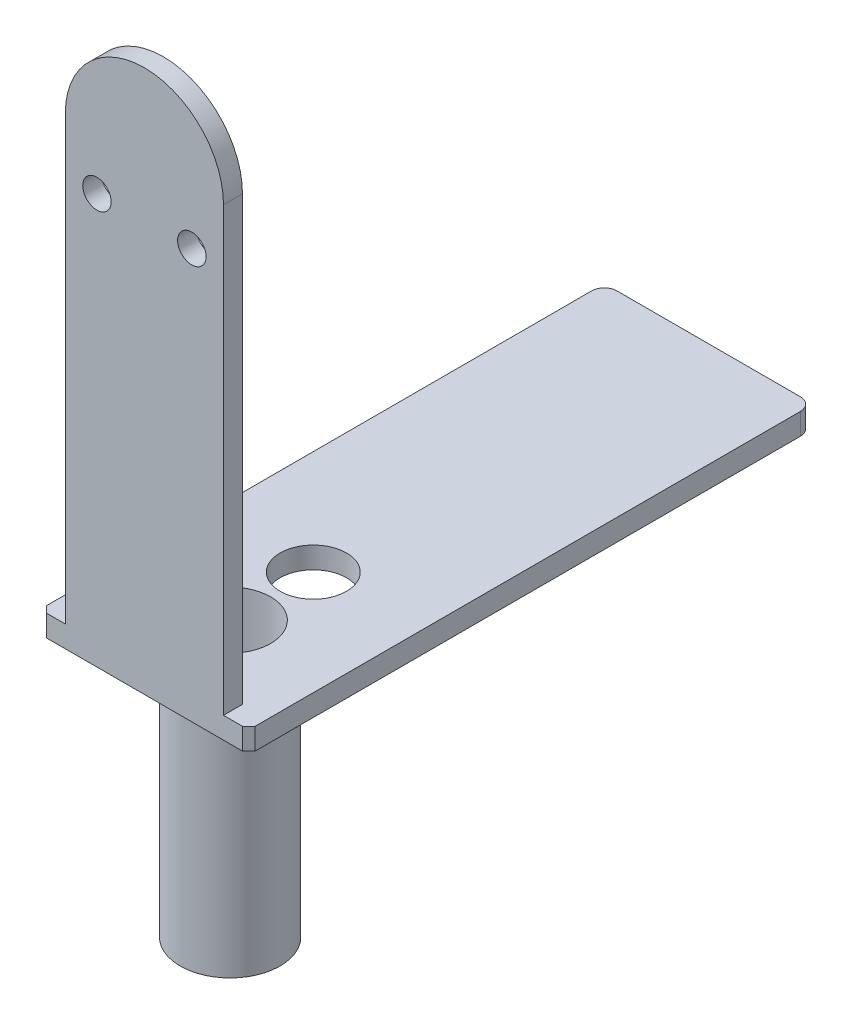
SolidWorks part; units mm, degrees
ref_plane "Front Plane" through (0, 0, 0) normal (0, 0, 1) x (1, 0, 0)
ref_plane "Top Plane" through (0, 0, 0) normal (0, 1, 0) x (1, 0, 0)
ref_plane "Right Plane" through (0, 0, 0) normal (1, 0, 0) x (0, 0, -1)
sketch "Sketch1" plane through (0, 0, 0) normal (0, 0, 1) x (1, 0, 0)
  line L0 (0, 0) -> (33, 0)
  line L1 (16.5, 0) -> (29, 0)
  line L2 (16.5, 0) -> (16.5, 9.4766)
  line L3 (4, 0) -> (4, 80.5)
  line L4 (29, 0) -> (29, 80.5)
  line L5 (0, 0) -> (0, 80.5)
  line L6 (0, 80.5) -> (4, 80.5)
  line L7 (33, 0) -> (33, 80.5)
  line L8 (33, 80.5) -> (29, 80.5)
  arc A0 (33, 80.5) -> (0, 80.5) centre (16.5, 80.5) ccw
  arc A1 (4, 80.5) -> (29, 80.5) centre (16.5, 80.5) cw
  point P5 (4, 0)
  dimension "D1" = 33
  dimension "D2" = 12.5
  dimension "D3" = 80.5
extrude "Boss-Extrude1" add sketch "Sketch1" along normal blind 71 contours L6 L5 L0 L3 | L6 A1 L8 A0 | L7 L8 L4 L0 region at (2, 40.25, 0) region at (16.5, 96.631, 0) region at (31, 40.25, 0)
sketch "Sketch2" plane through (0, 0, 71) normal (0, 0, 1) x (1, 0, 0)
  line L2 (33, 48.5) -> (0, 48.5)
  line L3 (0, 0) -> (0, 80.5) construction
  line L4 (0, 48.5) -> (0, 80.5)
  line L5 (33, 0) -> (33, 80.5) construction
  line L6 (33, 48.5) -> (33, 80.5)
  arc A0 (33, 80.5) -> (0, 80.5) centre (16.5, 80.5) ccw construction
  arc A1 (33, 80.5) -> (0, 80.5) centre (16.5, 80.5) ccw
  point P8 (16.5, 48.5)
extrude "Boss-Extrude2" add sketch "Sketch2" against normal blind 4
sketch "Sketch3" plane through (0, 0, 67) normal (0, 0, -1) x (-1, 0, 0)
  line L0 (-4, 48.5) -> (-29, 48.5) construction
  line L1 (-4, 48.5) -> (-29, 48.5)
  line L3 (-29, 44.5) -> (-4, 44.5)
  line L5 (0, 0) -> (0, 80.5) construction
  line L6 (0, 0) -> (0, 48.5)
  line L7 (-4, 48.5) -> (0, 48.5)
  line L8 (0, 0) -> (-3.8379, 0)
  line L9 (-4, 44.5) -> (-3.8379, 0)
  line L10 (-16.5, 44.5) -> (-16.5, 41.0104)
  line L11 (-33, 0) -> (-33, 48.5)
  line L12 (-29, 48.5) -> (-33, 48.5)
  line L13 (-29, 44.5) -> (-29.1621, 0)
  line L14 (-33, 0) -> (-29.1621, 0)
  line M8 (-29, 48.5) -> (-4, 48.5)
extrude "Boss-Extrude3" add sketch "Sketch3" against normal blind 34.2 contours L11 L14 L13 L3 L9 L8 L6 L7 L12 M8 region at (2, 47.9134, 67)
sketch "Sketch4" plane through (0, 0, 0) normal (0, 0, -1) x (-1, 0, 0)
  line L6 (-4, 80.5) -> (-4, 0)
  line L7 (-4, 0) -> (0, 0)
  line L8 (0, 0) -> (0, 80.5)
  line L9 (-33, 80.5) -> (-33, 0)
  line L10 (-33, 0) -> (-29, 0)
  line L11 (-29, 0) -> (-29, 80.5)
  line L12 (-4, 80.5) -> (-4, 0)
  line L13 (-4, 0) -> (0, 0)
  line L14 (0, 0) -> (0, 80.5)
  line L15 (-33, 80.5) -> (-33, 0)
  line L16 (-33, 0) -> (-29, 0)
  line L17 (-29, 0) -> (-29, 80.5)
  arc A2 (0, 80.5) -> (-33, 80.5) centre (-16.5, 80.5) ccw
  arc A3 (-4, 80.5) -> (-29, 80.5) centre (-16.5, 80.5) ccw
  arc A4 (0, 80.5) -> (-33, 80.5) centre (-16.5, 80.5) ccw
  arc A5 (-4, 80.5) -> (-29, 80.5) centre (-16.5, 80.5) ccw
  dimension "D1" = 0
extrude "Cut-Extrude1" cut sketch "Sketch4" against normal blind 13
sketch "Sketch5" plane through (0, 0, 71) normal (0, 0, 1) x (1, 0, 0)
  line L0 (0, 80.5) -> (33, 80.5)
  circle A0 centre (16.5, 80.5) radius 10
  dimension "D1" = 20
extrude "Cut-Extrude2" cut sketch "Sketch5" against normal blind 13 contours L0 A0 | L0 A0 region at (16.5, 84.7441, 71) region at (16.5, 76.2559, 71)
sketch "Sketch6" plane through (0, 0, 71) normal (0, 0, 1) x (1, 0, 0)
  line L0 (16.5, 70.5) -> (16.5, 73.1374)
  line L1 (16.5, 70.5) -> (33, 70.5)
  line L2 (33, 48.5) -> (33, 80.5) construction
  circle A0 centre (26.5, 70.5) radius 1.7
  circle A1 centre (6.5, 70.5) radius 1.7
  dimension "D2" = 3.4
  dimension "D1" = 6.5
extrude "Cut-Extrude3" cut sketch "Sketch6" against normal blind 13 contours A1 | L1 A0 | L1 A0 region at (26.5, 71.2215, 71) region at (26.5, 69.7785, 71) region at (6.5, 70.5, 71)
sketch "Sketch7" plane through (0, 0, 71) normal (0, 0, 1) x (1, 0, 0)
  circle A0 centre (6.5, 70.5) radius 3.25
  circle A1 centre (26.5, 70.5) radius 3.25
  dimension "D1" = 6.5
extrude "Cut-Extrude4" cut sketch "Sketch7" against normal blind 2.5
sketch "Sketch9" plane through (0, 0, 0) normal (0, -1, 0) x (1, 0, 0)
  line L0 (29.1621, 101.2) -> (29.1621, 71) construction
  line L1 (29.1621, 101.2) -> (29.1621, 71)
  line L2 (29.1621, 71) -> (29, 71)
  line L3 (29, 71) -> (29, 120)
  line L4 (29, 120) -> (29.1621, 101.2)
  line L6 (29, 67) -> (4, 67) construction
  line L7 (29, 67) -> (4, 67)
  line L8 (16.5, 67) -> (16.5, 71)
  line L9 (4, 120) -> (3.8379, 101.2)
  line L10 (4, 71) -> (4, 120)
  line L11 (3.8379, 71) -> (4, 71)
  line L12 (3.8379, 101.2) -> (3.8379, 71)
extrude "Boss-Extrude4" add sketch "Sketch9" against normal up to surface (44.5 mm away) contours L4 L1 L2 L3 | L9 L12 L11 L10 up to face at (16.5, 44.5, 79.7333)
sketch "Sketch10" plane through (0, 0, 101.2) normal (0, 0, 1) x (1, 0, 0)
  line L1 (40.2439, -6.5645) -> (-5.7585, -6.5645)
  line L2 (40.2439, -6.5645) -> (40.2439, 55.1467)
  line L3 (40.2439, 55.1467) -> (-5.7585, 55.1467)
  line L4 (-5.7585, -6.5645) -> (-5.7585, 55.1467)
  line L5 (40.2439, -6.5645) -> (-5.7585, 55.1467) construction
  line L6 (40.2439, 55.1467) -> (-5.7585, -6.5645) construction
  point P0 (17.2427, 24.2911)
extrude "Cut-Extrude5" cut sketch "Sketch10" along normal blind 42
fillet "Fillet1" radius 18 2 edges at (16.5, 44.5, 67) (16.5, 48.5, 71)
sketch "Sketch11" plane through (0, 0, 101.2) normal (0, 0, 1) x (1, 0, 0)
  line L0 (29, 0) -> (4, 0)
  line L8 (4, 44.5) -> (29, 44.5)
  line L9 (29, 44.5) -> (29, 0)
  line L10 (29, 0) -> (33, 0)
  line L11 (33, 0) -> (33, 48.5)
  line L12 (33, 48.5) -> (0, 48.5)
  line L13 (0, 48.5) -> (0, 0)
  line L14 (0, 0) -> (4, 0)
  line L15 (4, 0) -> (4, 44.5)
  line L18 (29, 0) -> (33, 0)
  line L19 (33, 0) -> (33, 48.5)
  line L20 (33, 48.5) -> (0, 48.5)
  line L21 (0, 48.5) -> (0, 0)
  line L22 (0, 0) -> (4, 0)
  dimension "D1" = 0
extrude "Boss-Extrude5" add sketch "Sketch11" along normal blind 4
fillet "Fillet3" radius 16.2 1 edges at (16.5, 48.5, 105.2)
fillet "Fillet4" radius 14 1 edges at (16.5, 44.5, 101.2)
sketch "Sketch12" plane through (0, 0, 0) normal (0, -1, 0) x (1, 0, 0)
  line L8 (4, 13) -> (4, 101.2)
  line L9 (4, 101.2) -> (29, 101.2)
  line L10 (29, 101.2) -> (29, 13)
  line L11 (29, 13) -> (33, 13)
  line L12 (33, 13) -> (33, 105.2)
  line L13 (33, 105.2) -> (0, 105.2)
  line L14 (0, 105.2) -> (0, 13)
  line L15 (0, 13) -> (4, 13)
  line L16 (4, 13) -> (4, 101.2)
  line L17 (4, 101.2) -> (29, 101.2)
  line L18 (29, 101.2) -> (29, 13)
  line L19 (29, 13) -> (33, 13)
  line L20 (33, 13) -> (33, 105.2)
  line L21 (33, 105.2) -> (0, 105.2)
  line L22 (0, 105.2) -> (0, 13)
  line L23 (0, 13) -> (4, 13)
  dimension "D1" = 0
extrude "Cut-Extrude6" cut sketch "Sketch12" against normal blind 10.6
sketch "Sketch13" plane through (0, 0, 13) normal (0, 0, -1) x (-1, 0, 0)
  line L6 (-33, 80.5) -> (-33, 10.6)
  line L7 (-33, 10.6) -> (-29, 10.6)
  line L8 (-29, 10.6) -> (-29, 80.5)
  line L9 (-4, 80.5) -> (-4, 10.6)
  line L10 (-4, 10.6) -> (0, 10.6)
  line L11 (0, 10.6) -> (0, 80.5)
  line L12 (-33, 80.5) -> (-33, 10.6)
  line L13 (-33, 10.6) -> (-29, 10.6)
  line L14 (-29, 10.6) -> (-29, 80.5)
  line L15 (-4, 80.5) -> (-4, 10.6)
  line L16 (-4, 10.6) -> (0, 10.6)
  line L17 (0, 10.6) -> (0, 80.5)
  arc A2 (-4, 80.5) -> (-29, 80.5) centre (-16.5, 80.5) ccw
  arc A3 (0, 80.5) -> (-33, 80.5) centre (-16.5, 80.5) ccw
  arc A4 (-4, 80.5) -> (-29, 80.5) centre (-16.5, 80.5) ccw
  arc A5 (0, 80.5) -> (-33, 80.5) centre (-16.5, 80.5) ccw
  dimension "D1" = 0
extrude "Boss-Extrude6" add sketch "Sketch13" along normal blind 4
ref_plane "Plane1" through (0, 0, 13) normal (0, 0, -1) x (-1, 0, 0)
sketch "Sketch14" plane through (0, 0, 13) normal (0, 0, -1) x (-1, 0, 0)
  line L0 (-29, 10.6) -> (-4, 10.6)
  line L6 (-33, 80.5) -> (-33, 10.6)
  line L7 (-33, 10.6) -> (-29, 10.6)
  line L8 (-29, 10.6) -> (-29, 80.5)
  line L9 (-4, 80.5) -> (-4, 10.6)
  line L10 (-4, 10.6) -> (0, 10.6)
  line L11 (0, 10.6) -> (0, 80.5)
  line L12 (-33, 80.5) -> (-33, 10.6)
  line L13 (-33, 10.6) -> (-29, 10.6)
  line L16 (-4, 10.6) -> (0, 10.6)
  line L17 (0, 10.6) -> (0, 80.5)
  arc A2 (0, 80.5) -> (-33, 80.5) centre (-16.5, 80.5) ccw
  arc A3 (-4, 80.5) -> (-29, 80.5) centre (-16.5, 80.5) ccw
  arc A4 (0, 80.5) -> (-33, 80.5) centre (-16.5, 80.5) ccw
  dimension "D1" = 0
extrude "Cut-Extrude7" cut sketch "Sketch14" against normal blind 148
sketch "Sketch15" plane through (0, 0, 13) normal (0, 0, 1) x (1, 0, 0)
  line L0 (4, 10.6) -> (29, 10.6)
  line L6 (29, 80.5) -> (29, 10.6)
  line L7 (29, 10.6) -> (33, 10.6)
  line L8 (33, 10.6) -> (33, 80.5)
  line L9 (0, 80.5) -> (0, 10.6)
  line L10 (0, 10.6) -> (4, 10.6)
  line L11 (4, 10.6) -> (4, 80.5)
  line L12 (29, 80.5) -> (29, 10.6)
  line L13 (29, 10.6) -> (33, 10.6)
  line L17 (4, 10.6) -> (4, 80.5)
  arc A2 (33, 80.5) -> (0, 80.5) centre (16.5, 80.5) ccw
  arc A3 (29, 80.5) -> (4, 80.5) centre (16.5, 80.5) ccw
  arc A5 (29, 80.5) -> (4, 80.5) centre (16.5, 80.5) ccw
  line M10 (29, 80.5) -> (29, 10.6)
  line M16 (4, 10.6) -> (4, 80.5)
  arc M17 (4, 80.5) -> (29, 80.5) centre (16.5, 80.5) cw
  dimension "D1" = 0
extrude "Boss-Extrude7" add sketch "Sketch15" along normal blind 3 separate body contours L0 M16 M10 M17 region at (16.5, 50.5076, 13)
sketch "Sketch16" plane through (0, 0, 9) normal (0, 0, -1) x (-1, 0, 0)
  line L6 (-33, 80.5) -> (-33, 10.6)
  line L7 (-33, 10.6) -> (-29, 10.6)
  line L8 (-29, 10.6) -> (-29, 80.5)
  line L9 (-4, 80.5) -> (-4, 10.6)
  line L10 (-4, 10.6) -> (0, 10.6)
  line L11 (0, 10.6) -> (0, 80.5)
  line L12 (-33, 80.5) -> (-33, 10.6)
  line L13 (-33, 10.6) -> (-29, 10.6)
  line L14 (-29, 10.6) -> (-29, 80.5)
  line L15 (-4, 80.5) -> (-4, 10.6)
  line L16 (-4, 10.6) -> (0, 10.6)
  line L17 (0, 10.6) -> (0, 80.5)
  arc A2 (0, 80.5) -> (-33, 80.5) centre (-16.5, 80.5) ccw
  arc A3 (-4, 80.5) -> (-29, 80.5) centre (-16.5, 80.5) ccw
  arc A4 (0, 80.5) -> (-33, 80.5) centre (-16.5, 80.5) ccw
  arc A5 (-4, 80.5) -> (-29, 80.5) centre (-16.5, 80.5) ccw
  dimension "D1" = 0
extrude "Cut-Extrude8" cut sketch "Sketch16" against normal blind 14
sketch "Sketch17" plane through (0, 0, 13) normal (0, 0, -1) x (-1, 0, 0)
  line L0 (-16.5, 93) -> (-16.5, 68)
  line L1 (-16.5, 68) -> (-4, 68)
  line L2 (-4, 10.6) -> (-4, 80.5) construction
  arc A0 (-4, 80.5) -> (-29, 80.5) centre (-16.5, 80.5) ccw construction
  circle A1 centre (-9, 72) radius 2.25
  circle A2 centre (-24, 72) radius 2.25
  dimension "D2" = 4.5
  dimension "D3" = 5
  dimension "D4" = 4
  dimension "D1" = 25
extrude "Cut-Extrude9" cut sketch "Sketch17" against normal blind 14 contours A2 | A1 region at (24, 72, 13)
sketch "Sketch18" plane through (0, 10.6, 0) normal (0, -1, 0) x (1, 0, 0)
  line L0 (29, 16) -> (29, -76.2)
  line L1 (29, 16) -> (4, 16)
  line L2 (4, 16) -> (4, -76.2)
  line L3 (4, -76.2) -> (29, -76.2)
  dimension "D1" = 92.2
extrude "Boss-Extrude8" add sketch "Sketch18" along normal blind 4
sketch "Sketch19" plane through (0, 6.6, 0) normal (0, -1, 0) x (1, 0, 0)
  line L0 (4, 16) -> (0, 16)
  line L1 (0, 16) -> (0, -76.2)
  line L2 (4, -76.2) -> (0, -76.2)
  line L3 (4, -76.2) -> (4, 16)
  line L4 (16.5, 16) -> (16.5, 9.1971)
  line L5 (29, 16) -> (4, 16) construction
  line L6 (29, -76.2) -> (33, -76.2)
  line L7 (33, 16) -> (33, -76.2)
  line L8 (29, 16) -> (33, 16)
  line L9 (29, -76.2) -> (29, 16)
  line M7 (4, 16) -> (4, -76.2)
  line M9 (29, -76.2) -> (29, 16)
extrude "Boss-Extrude9" add sketch "Sketch19" against normal up to surface (4 mm away) contours L2 L0 L1 M7 | L8 L6 L7 M9 region at (2, 6.6, -30.1) region at (31, 6.6, -30.1) up to face at (16.5, 10.6, -31.6)
sketch "Sketch20" plane through (0, 6.6, 0) normal (0, -1, 0) x (1, 0, 0)
  line L0 (16.5, 16) -> (16.5, -10.7)
  line L1 (33, 16) -> (0, 16) construction
  circle A0 centre (16.5, -10.7) radius 5.25
  dimension "D2" = 10.5
  dimension "D1" = 26.7
extrude "Cut-Extrude10" cut sketch "Sketch20" against normal up to surface (4 mm away) contours A0 region at (12.8927, 6.6, -14.3073) up to face at (16.5, 10.6, -7.8)
sketch "Sketch21" plane through (0, 6.6, 0) normal (0, -1, 0) x (1, 0, 0)
  line L4 (33, 16) -> (0, 16)
  line L5 (0, 16) -> (0, -76.2)
  line L6 (0, -76.2) -> (33, -76.2)
  line L7 (33, -76.2) -> (33, 16)
  line L8 (33, 16) -> (0, 16)
  line L9 (0, 16) -> (0, -76.2)
  line L10 (0, -76.2) -> (33, -76.2)
  line L11 (33, -76.2) -> (33, 16)
  dimension "D1" = 0
extrude "Cut-Extrude11" cut sketch "Sketch21" against normal blind 0.6
sketch "Sketch22" plane through (0, 7.2, 0) normal (0, -1, 0) x (1, 0, 0)
  line L0 (16.5, 16) -> (16.5, 1.3)
  line L1 (33, 16) -> (0, 16) construction
  circle A0 centre (16.5, 1.3) radius 5.25
  dimension "D2" = 10.5
  dimension "D1" = 14.7
extrude "Cut-Extrude12" cut sketch "Sketch22" against normal up to surface (3.4 mm away) contours A0 region at (12.8927, 7.2, -2.3073) up to face at (16.5, 10.6, -15.95)
sketch "Sketch23" plane through (0, 7.2, 0) normal (0, -1, 0) x (1, 0, 0)
  line L0 (16.5, -5.45) -> (16.5, 10.35)
  circle A0 centre (16.5, -10.7) radius 5.25 construction
  circle A1 centre (16.5, 2.45) radius 7.9
  circle A2 centre (16.5, 2.45) radius 6.4
  dimension "D1" = 15.8
extrude "Boss-Extrude10" add sketch "Sketch23" along normal blind 40 contours A2 L0 A1 | A2 L0 A1 region at (8.7766, 7.2, 2.45) region at (16.6766, 7.2, -4.7)
sketch "Sketch24" plane through (0, 7.2, 0) normal (0, -1, 0) x (1, 0, 0)
  circle A2 centre (16.5, 2.45) radius 6.4 construction
  circle A3 centre (16.5, 2.45) radius 6.4
extrude "Cut-Extrude13" cut sketch "Sketch24" against normal up to surface (3.4 mm away) up to face at (16.5, 10.6, -3.95)
sketch "Sketch25" plane through (0, 10.6, 0) normal (0, 1, 0) x (1, 0, 0)
  line L0 (16.5, 76.2) -> (16.5, 74.7)
  line L1 (0, 76.2) -> (33, 76.2) construction
  line L2 (16.5, 74.7) -> (6.5, 74.7)
  line L3 (6.5, 74.7) -> (6.5, 72.7)
  line L4 (16.5, 74.7) -> (26.5, 74.7)
  line L5 (26.5, 74.7) -> (26.5, 72.7)
  line L6 (26.5, 72.7) -> (6.5, 72.7)
extrude "Boss-Extrude11" add sketch "Sketch25" along normal blind 15 contours L6 L5 L4 L2 L3 region at (16.5, 10.6, -73.7)
sketch "Sketch26" plane through (0, 10.6, 0) normal (0, 1, 0) x (1, 0, 0)
  line L0 (21.5, 74.7) -> (11.5, 74.7)
  line L1 (6.5, 74.7) -> (26.5, 74.7) construction
  line L2 (11.5, 74.7) -> (16.5, 74.7)
  line L3 (11.5, 74.7) -> (11.5, 76.2)
  line L4 (0, 76.2) -> (33, 76.2) construction
  line L5 (11.5, 76.2) -> (21.5, 76.2)
  line L6 (21.5, 76.2) -> (21.5, 74.7)
  point P5 (16.5, 74.7)
  dimension "D1" = 10
extrude "Boss-Extrude12" add sketch "Sketch26" along normal up to surface (15 mm away) contours L3 L5 L6 L0 up to face at (16.5, 25.6, -73.7)
sketch "Sketch27" plane through (0, 10.6, 0) normal (0, 1, 0) x (1, 0, 0)
  line L8 (6.5, 72.7) -> (26.5, 72.7)
  line L9 (26.5, 72.7) -> (26.5, 74.7)
  line L10 (26.5, 74.7) -> (21.5, 74.7)
  line L11 (21.5, 74.7) -> (21.5, 76.2)
  line L12 (21.5, 76.2) -> (11.5, 76.2)
  line L13 (11.5, 76.2) -> (11.5, 74.7)
  line L14 (11.5, 74.7) -> (6.5, 74.7)
  line L15 (6.5, 74.7) -> (6.5, 72.7)
  line L16 (6.5, 72.7) -> (26.5, 72.7)
  line L17 (26.5, 72.7) -> (26.5, 74.7)
  line L18 (26.5, 74.7) -> (21.5, 74.7)
  line L19 (21.5, 74.7) -> (21.5, 76.2)
  line L20 (21.5, 76.2) -> (11.5, 76.2)
  line L21 (11.5, 76.2) -> (11.5, 74.7)
  line L22 (11.5, 74.7) -> (6.5, 74.7)
  line L23 (6.5, 74.7) -> (6.5, 72.7)
  dimension "D1" = 0
extrude "Cut-Extrude14" cut sketch "Sketch27" along normal up to surface (15 mm away) up to face at (16.5, 25.6, -74.575)
sketch "Sketch28" plane through (0, 0, -76.2) normal (0, 0, -1) x (-1, 0, 0)
  line L4 (0, 10.6) -> (-33, 10.6)
  line L5 (-33, 10.6) -> (-33, 7.2)
  line L6 (-33, 7.2) -> (0, 7.2)
  line L7 (0, 7.2) -> (0, 10.6)
  line L8 (0, 10.6) -> (-33, 10.6)
  line L9 (-33, 10.6) -> (-33, 7.2)
  line L10 (-33, 7.2) -> (0, 7.2)
  line L11 (0, 7.2) -> (0, 10.6)
  dimension "D1" = 0
extrude "Cut-Extrude15" cut sketch "Sketch28" against normal blind 3
chamfer "Chamfer1" distance 1 angle 45 2 edges at (0, 8.9, 16) (33, 8.9, 16)
fillet "Fillet5" radius 2 2 edges at (0, 8.9, -73.2) (33, 8.9, -73.2)
